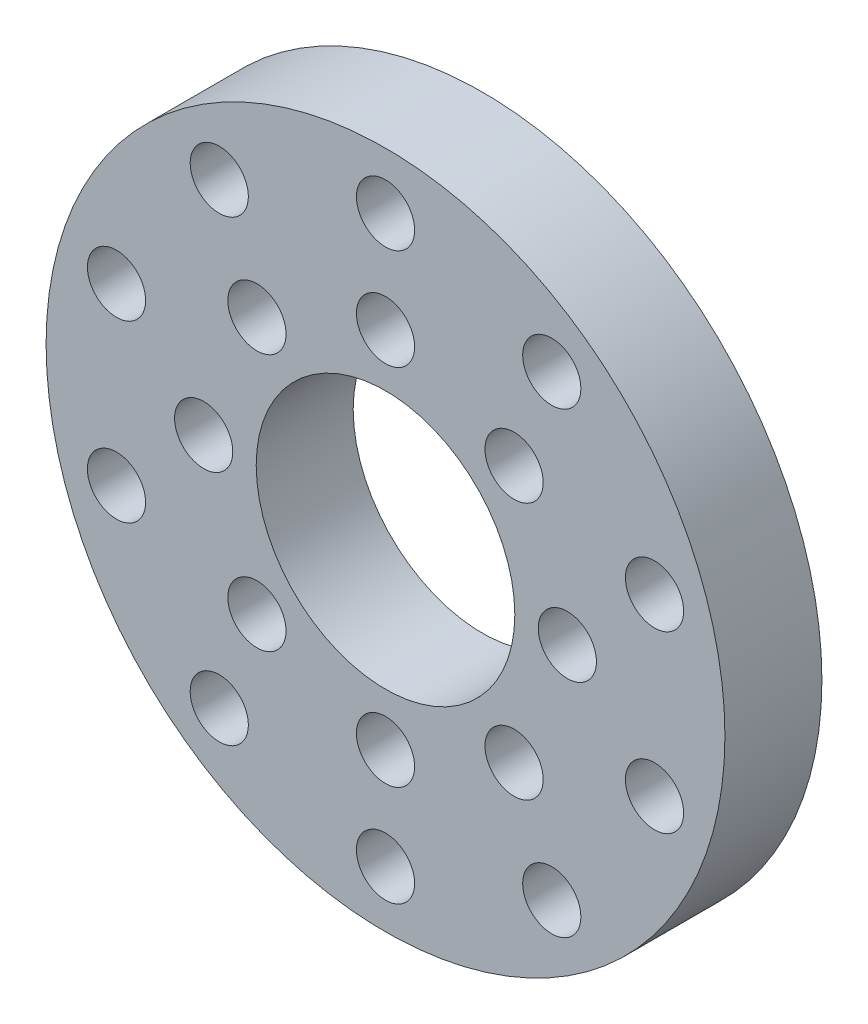
SolidWorks part; units mm, degrees
ref_plane "前视基准面" through (0, 0, 0) normal (0, 0, 1) x (1, 0, 0)
ref_plane "上视基准面" through (0, 0, 0) normal (0, 1, 0) x (1, 0, 0)
ref_plane "右视基准面" through (0, 0, 0) normal (1, 0, 0) x (0, 0, -1)
sketch "草图1" plane through (0, 0, 0) normal (0, 0, 1) x (1, 0, 0)
  circle A0 centre (0, 0) radius 21
  dimension "D1" = 42
extrude "凸台-拉伸1" add sketch "草图1" along normal blind 6
sketch "草图2" plane through (0, 0, 0) normal (0, 0, -1) x (-1, 0, 0)
  circle A0 centre (0, 0) radius 8
  dimension "D1" = 16
extrude "切除-拉伸1" cut sketch "草图2" against normal blind 8
hole_wizard "打孔尺寸(%根据)内六角圆柱头螺钉的类型1" positions "草图8" profile "草图7" counterbore size "M3" standard "GB"
sketch "草图8" plane through (0, 0, 0) normal (0, 0, -1) x (-1, 0, 0)
  line L1 (0, 0) -> (0, 23.6243) construction
  circle A0 centre (0, 0) radius 11.25 construction
  point P0 (0, 11.25)
  dimension "D1" = 22.5
sketch "草图7" plane through (0, 11.25, 0) normal (1, 0, 0) x (0, 1, 0)
  line L0 (0, 0) -> (0, 8.5815)
  line L1 (0, 8.5815) -> (1.8, 7.5)
  line L2 (1.8, 7.5) -> (1.8, 3.4)
  line L3 (1.8, 3.4) -> (3, 3.4)
  line L4 (3, 3.4) -> (3, 0)
  line L5 (3, 0) -> (0, 0)
  line L10 (0, 8.5815) -> (-1.8, 7.5) construction
  line L11 (0, -6.35) -> (0, 107.95) construction
  dimension "孔直径" = 3.6
  dimension "孔深度" = 7.5
  dimension "柱形沉头孔直径" = 6
  dimension "柱形沉头孔深度" = 3.4
  dimension "导头角度" = 118
ref_axis "基准轴1" through (0, 0, 6) along (0, 0, -1)
pattern_circular "阵列(圆周)1" count 8 over 360 about axis through (0, 0, 6) along (0, 0, -1) of "打孔尺寸(%根据)内六角圆柱头螺钉的类型1"
hole_wizard "打孔尺寸(%根据)内六角圆柱头螺钉的类型7" positions "草图14" profile "草图13" counterbore size "M3" standard "GB"
sketch "草图14" plane through (0, 0, 0) normal (0, 0, -1) x (-1, 0, 0)
  line L0 (0, 0) -> (0, 23.6964) construction
  circle A0 centre (0, 0) radius 17.5 construction
  point P0 (0, 17.5)
  dimension "D1" = 35
sketch "草图13" plane through (0, 17.5, 0) normal (1, 0, 0) x (0, 1, 0)
  line L0 (0, 0) -> (0, 8.5815)
  line L1 (0, 8.5815) -> (1.8, 7.5)
  line L2 (1.8, 7.5) -> (1.8, 3.4)
  line L3 (1.8, 3.4) -> (3, 3.4)
  line L4 (3, 3.4) -> (3, 0)
  line L5 (3, 0) -> (0, 0)
  line L10 (0, 8.5815) -> (-1.8, 7.5) construction
  line L11 (0, -6.35) -> (0, 107.95) construction
  dimension "孔直径" = 3.6
  dimension "孔深度" = 7.5
  dimension "柱形沉头孔直径" = 6
  dimension "柱形沉头孔深度" = 3.4
  dimension "导头角度" = 118
pattern_circular "阵列(圆周)2" count 10 over 360 about axis through (0, 0, 6) along (0, 0, -1) of "打孔尺寸(%根据)内六角圆柱头螺钉的类型7"
